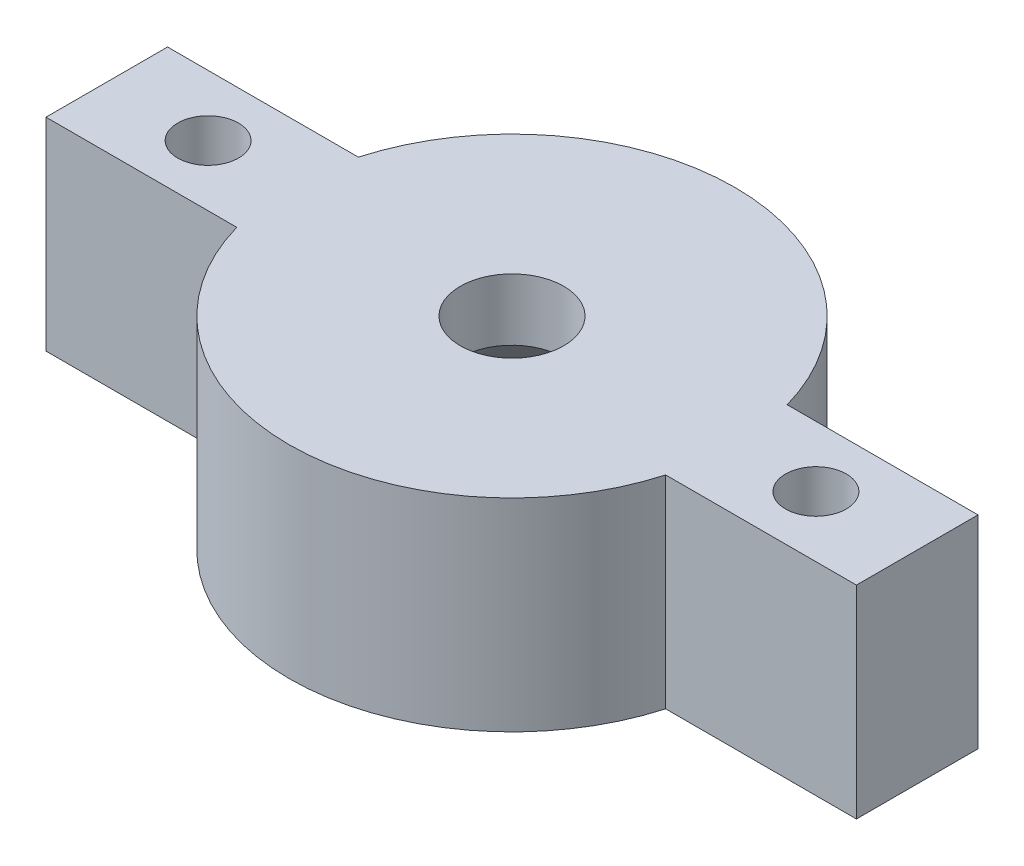
SolidWorks part; units mm, degrees
ref_plane "Front Plane" through (0, 0, 0) normal (0, 0, 1) x (1, 0, 0)
ref_plane "Top Plane" through (0, 0, 0) normal (0, 1, 0) x (1, 0, 0)
ref_plane "Right Plane" through (0, 0, 0) normal (1, 0, 0) x (0, 0, -1)
sketch "Sketch2" plane through (0, 0, 0) normal (1, 0, 0) x (0, 0, -1)
  line L1 (-3, -5) -> (3, -5)
  line L2 (-3, -5) -> (-3, 5)
  line L3 (-3, 5) -> (3, 5)
  line L4 (3, -5) -> (3, 5)
  line L5 (-3, -5) -> (3, 5) construction
  line L6 (-3, 5) -> (3, -5) construction
  point P0 (0, 0)
  dimension "D1" = 6
  dimension "D2" = 10
extrude "Boss-Extrude1" add sketch "Sketch2" along normal blind 40
sketch "Sketch3" plane through (0, 5, 0) normal (0, 1, 0) x (1, 0, 0)
  line L0 (0, 0) -> (40, 0) construction
  line L1 (40, 3) -> (40, -3) construction
  circle A0 centre (20, 0) radius 11
  dimension "D1" = 22
extrude "Boss-Extrude2" add sketch "Sketch3" against normal up to surface (10 mm away) up to face at (20, -5, 0)
sketch "Sketch4" plane through (0, -5, 0) normal (0, -1, 0) x (-1, 0, 0)
  circle A0 centre (-20, 0) radius 7.5
  circle A1 centre (-20, 0) radius 11 construction
  dimension "D1" = 15
extrude "Cut-Extrude1" cut sketch "Sketch4" against normal blind 2
sketch "Sketch5" plane through (0, 0, 0) normal (0, 0, -1) x (-1, 0, 0)
  line L0 (-20, -3) -> (-27.5, -3)
  line L2 (-27.5, -3) -> (-22.5, 2)
  line L3 (-22.5, 2) -> (-20, 2)
  line L5 (-20, 2) -> (-20, -3)
  line L6 (-30.583, -5) -> (-9.417, -5) construction
  line L7 (-9.417, 5) -> (-30.583, 5) construction
  point P10 (-20, 5)
  dimension "D1" = 2
  dimension "D2" = 7.5
  dimension "D3" = 2.5
  dimension "D4" = 5
revolve "Cut-Revolve1" cut sketch "Sketch5" angle 360 about L5
sketch "Sketch6" plane through (0, 2, 0) normal (0, -1, 0) x (1, 0, 0)
  circle A0 centre (20, 0) radius 2.55
  circle A1 centre (20, 0) radius 2.5 construction
  dimension "D1" = 5.1
extrude "Cut-Extrude2" cut sketch "Sketch6" against normal through all both and the other way through all contours A0
fillet "Fillet1" radius 2 1 edges at (20, -5, -7.5)
sketch "Sketch7" plane through (0, -5, 0) normal (0, -1, 0) x (1, 0, 0)
  line L0 (0, 3) -> (0, -3) construction
  line L1 (20, 11) -> (20, -11) construction
  circle A0 centre (5, 0) radius 1.5
  arc A1 (30.583, 3) -> (9.417, 3) centre (20, 0) ccw construction
  arc A2 (9.417, -3) -> (30.583, -3) centre (20, 0) ccw construction
  circle A3 centre (35, 0) radius 1.5
  dimension "D1" = 3
  dimension "D2" = 5
extrude "Cut-Extrude3" cut sketch "Sketch7" against normal up to next
